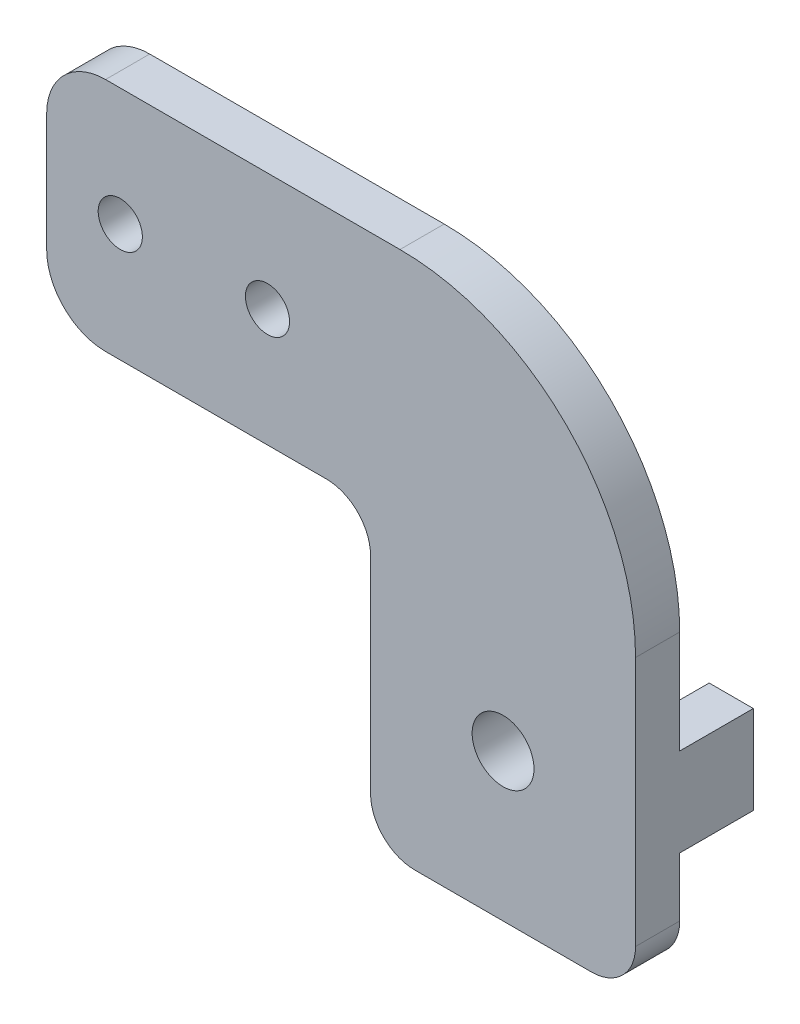
SolidWorks part; units mm, degrees
ref_plane "前视基准面" through (0, 0, 0) normal (0, 0, 1) x (1, 0, 0)
ref_plane "上视基准面" through (0, 0, 0) normal (0, 1, 0) x (1, 0, 0)
ref_plane "右视基准面" through (0, 0, 0) normal (1, 0, 0) x (0, 0, -1)
sketch "草图1" plane through (0, 0, 0) normal (0, 0, 1) x (1, 0, 0)
  line L0 (-1000, 0) -> (49000, 0) construction
  line L1 (0, -1000) -> (0, 49000) construction
  line L2 (-1000, 20) -> (49000, 20) construction
  line L3 (26, 20) -> (26, 0) construction
  line L4 (-4, 0) -> (-4, 40.5512) construction
  line L5 (8, 36) -> (28, 36)
  line L6 (4, 0) -> (4, 40.5512) construction
  line L7 (44, 20) -> (44, 3)
  line L8 (29, 0) -> (41, 0)
  line L9 (26, 3) -> (26, 17)
  line L10 (23, 20) -> (8, 20)
  line L11 (4, 24) -> (4, 32)
  line L12 (-971, 10) -> (49029, 10) construction
  line L13 (14, -985) -> (14, 49015) construction
  line L14 (26, 13) -> (29, 13)
  line L15 (26, 13) -> (26, 7)
  line L16 (26, 7) -> (29, 7)
  line L17 (29, 13) -> (29, 7)
  line L18 (41, 13) -> (44, 13)
  line L19 (41, 13) -> (41, 7)
  line L20 (41, 7) -> (44, 7)
  line L21 (44, 13) -> (44, 7)
  circle A0 centre (35, 10) radius 2.1
  circle A1 centre (35, 10) radius 6 construction
  circle A2 centre (9, 28) radius 1.5
  circle A3 centre (19, 28) radius 1.5
  arc A4 (28, 36) -> (44, 20) centre (28, 20) cw
  arc A5 (44, 3) -> (41, 0) centre (41, 3) cw
  arc A6 (29, 0) -> (26, 3) centre (29, 3) cw
  arc A7 (8, 20) -> (4, 24) centre (8, 24) cw
  arc A8 (8, 36) -> (4, 32) centre (8, 32) ccw
  arc A9 (23, 20) -> (26, 17) centre (23, 17) cw
  point P43 (44, 0)
  point P46 (26, 0)
  point P49 (4, 20)
  point P52 (4, 36)
  dimension "D9" = 4.2
  dimension "D12" = 12
  dimension "D14" = 3
  dimension "D16" = 16
  dimension "D17" = 3
  dimension "D18" = 4
  dimension "D19" = 3
  dimension "D1" = 8
  dimension "D2" = 20
  dimension "D3" = 26
  dimension "D4" = 0
  dimension "D5" = 0
  dimension "D6" = 16
  dimension "D7" = 18
  dimension "D8" = 10
  dimension "D10" = 9
  dimension "D11" = 6
  dimension "D13" = 8
  dimension "D15" = 10
  dimension "D20" = 10
extrude "凸台-拉伸1" add sketch "草图1" along normal blind 3 contours L10 A9 L14 L17 L16 A6 L8 A5 L20 L19 L18 L7 A4 L5 A8 L11 A7 A3 A2 A0 | L19 L20 L7 L18 | L17 L14 L9 L16 region at (27.1433, 21.423, 0) region at (42.5, 10, 0) region at (27.5, 10, 0)
extrude "凸台-拉伸2" add sketch "草图1<3>" against normal blind 5 contours L19 L20 L7 L18 | L17 L14 L9 L16 region at (42.5, 10, 0) region at (27.5, 10, 0)
sketch "草图1<3>" plane through (0, 0, 0) normal (0, 0, 1) x (1, 0, 0) same geometry as "草图1"
